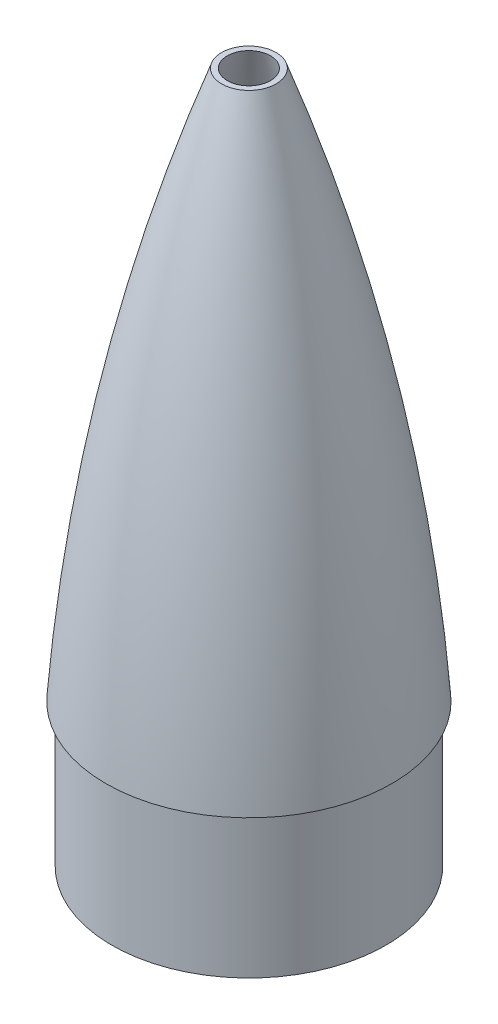
SolidWorks part; units mm, degrees
material "PVB"
ref_plane "Front Plane" through (0, 0, 0) normal (0, 0, 1) x (1, 0, 0)
ref_plane "Top Plane" through (0, 0, 0) normal (0, 1, 0) x (1, 0, 0)
ref_plane "Right Plane" through (0, 0, 0) normal (1, 0, 0) x (0, 0, -1)
sketch "Sketch2" plane through (0, 0, 0) normal (0, 0, 1) x (1, 0, 0)
  line L0 (0, 0) -> (0, 330.2) construction
  line L1 (-76.2, 0) -> (-69.85, 0)
  line L2 (0, 330.2) -> (0, 325.12)
  arc A0 (0, 330.2) -> (-76.2, 0) centre (1014.3906, -77.7824) ccw
  arc A1 (0, 325.12) -> (-69.85, 0) centre (1133.5772, -88.4854) ccw
  dimension "D1" = 330.2
  dimension "D2" = 5.08
  dimension "D3" = 76.2
  dimension "D4" = 6.35
revolve "Revolve1" add sketch "Sketch2" angle 360 about L2
ref_plane "Plane2" through (0, 381, 0) normal (0, 1, 0) x (1, 0, 0)
sketch "Sketch7" plane through (0, 381, 0) normal (0, 1, 0) x (1, 0, 0)
  circle A0 centre (0, 0) radius 317.5
  dimension "D1" = 635
extrude "Cut-Extrude2" cut sketch "Sketch7" against normal blind 88.9
sketch "Sketch8" plane through (0, 0, 0) normal (0, -1, 0) x (1, 0, 0)
  circle A0 centre (0, 0) radius 69.85
  circle A1 centre (0, 0) radius 73.025
  dimension "D1" = 146.05
extrude "Boss-Extrude1" add sketch "Sketch8" along normal blind 76.2
